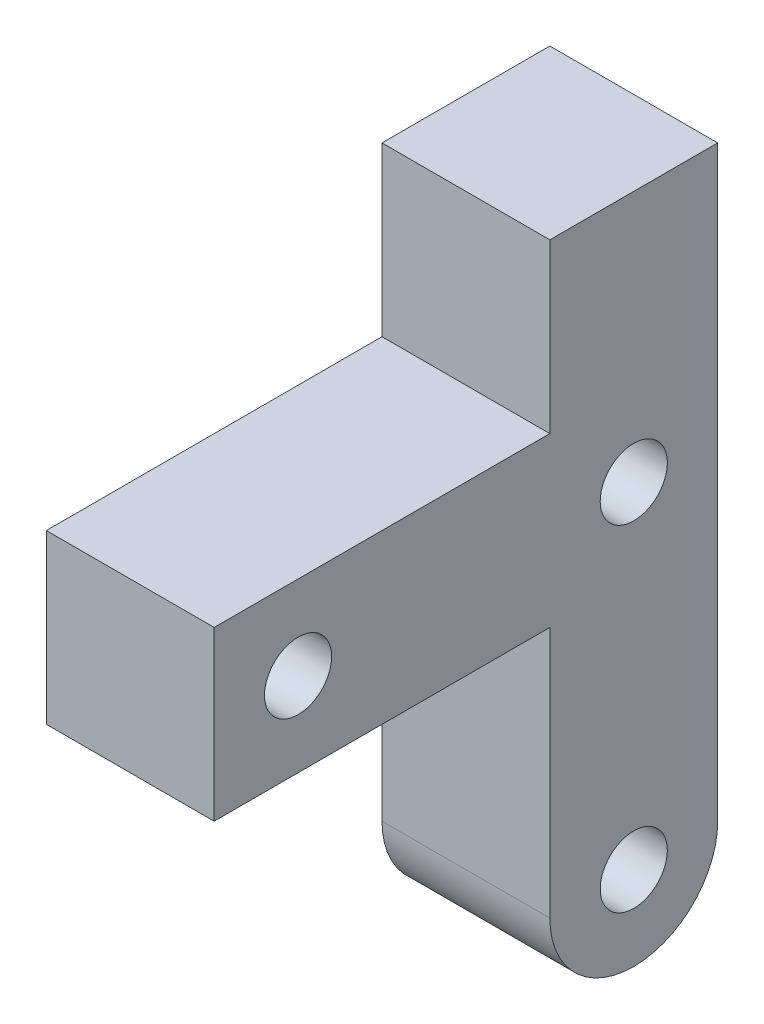
SolidWorks part; units mm, degrees
ref_plane "Front Plane" through (0, 0, 0) normal (0, 0, 1) x (1, 0, 0)
ref_plane "Top Plane" through (0, 0, 0) normal (0, 1, 0) x (1, 0, 0)
ref_plane "Right Plane" through (0, 0, 0) normal (1, 0, 0) x (0, 0, -1)
sketch "Sketch1" plane through (0, 0, 0) normal (0, 0, 1) x (1, 0, 0)
  line L1 (0, 0) -> (10, 0)
  line L2 (0, 0) -> (0, 40)
  line L3 (0, 40) -> (10, 40)
  line L4 (10, 0) -> (10, 40)
  dimension "D1" = 40
  dimension "D2" = 10
extrude "Boss-Extrude1" add sketch "Sketch1" along normal blind 10
sketch "Sketch2" plane through (10, 0, 0) normal (1, 0, 0) x (0, 0, -1)
  line L0 (-10, 0) -> (-10, 40) construction
  line L1 (-10, 0) -> (0, 0) construction
  circle A0 centre (-5, 5) radius 2
  point P4 (-5, 0)
  dimension "D1" = 4
  dimension "D2" = 5
  dimension "D3" = 5
extrude "Cut-Extrude1" cut sketch "Sketch2" against normal up to next
sketch "Sketch3" plane through (0, 0, 10) normal (0, 0, 1) x (1, 0, 0)
  line L0 (0, 40) -> (0, 0) construction
  line L1 (0, 30) -> (10, 30)
  line L2 (0, 30) -> (0, 20)
  line L3 (0, 20) -> (10, 20)
  line L4 (10, 30) -> (10, 20)
  line L5 (10, 0) -> (10, 40) construction
  dimension "D1" = 10
extrude "Boss-Extrude2" add sketch "Sketch3" along normal blind 20
sketch "Sketch4" plane through (0, 0, 0) normal (-1, 0, 0) x (0, 0, 1)
  line L0 (30, 30) -> (30, 20) construction
  line L1 (30, 20) -> (10, 20) construction
  circle A0 centre (25, 25) radius 2
  dimension "D1" = 4
  dimension "D2" = 5
  dimension "D3" = 5
extrude "Cut-Extrude2" cut sketch "Sketch4" against normal up to next
sketch "Sketch5" plane through (0, 0, 0) normal (-1, 0, 0) x (0, 0, 1)
  line L0 (0, 40) -> (0, 0) construction
  line L1 (30, 20) -> (10, 20) construction
  circle A0 centre (5, 25) radius 2
  dimension "D1" = 4
  dimension "D2" = 5
  dimension "D3" = 5
extrude "Cut-Extrude3" cut sketch "Sketch5" against normal through all
fillet "Fillet1" radius 5 2 edges at (5, 0, 0) (5, 0, 10)
